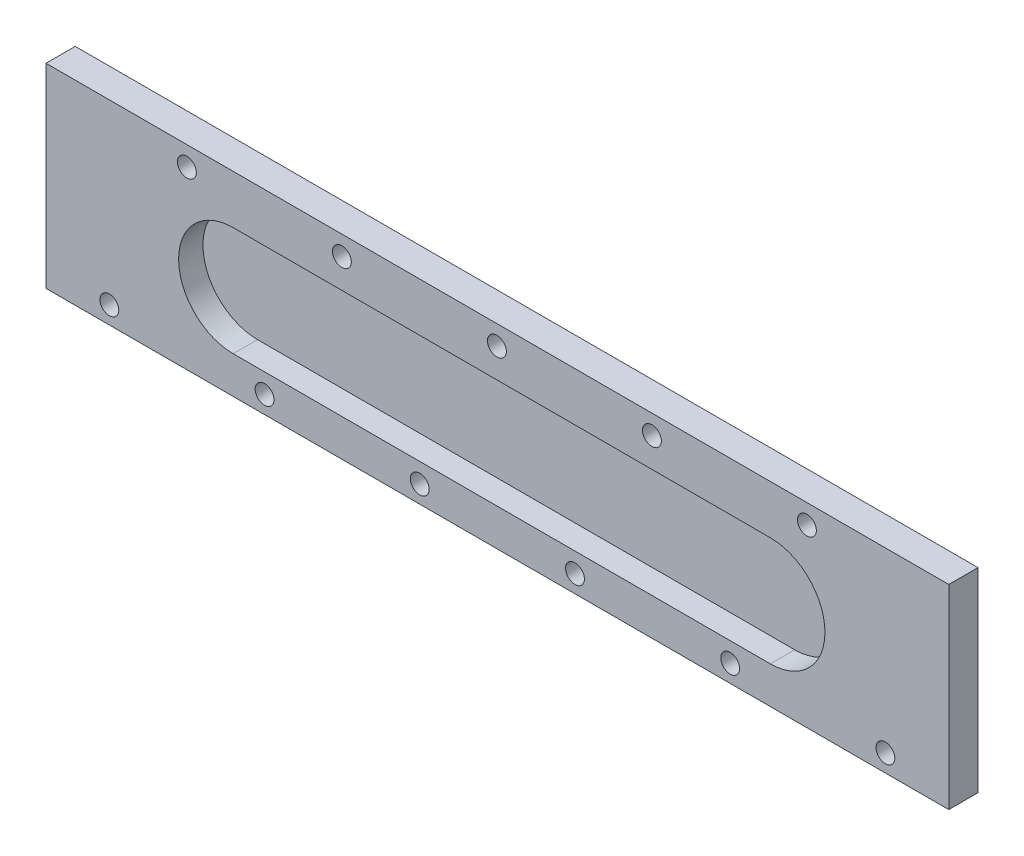
SolidWorks part; units mm, degrees
ref_plane "Front Plane" through (0, 0, 0) normal (0, 0, 1) x (1, 0, 0)
ref_plane "Top Plane" through (0, 0, 0) normal (0, 1, 0) x (1, 0, 0)
ref_plane "Right Plane" through (0, 0, 0) normal (1, 0, 0) x (0, 0, -1)
sketch "Sketch5" plane through (0, 0, 0) normal (0, 0, 1) x (1, 0, 0)
  line L1 (0, 0) -> (-235.204, 0)
  line L2 (0, 0) -> (0, 50.8)
  line L3 (0, 50.8) -> (-235.204, 50.8)
  line L4 (-235.204, 0) -> (-235.204, 50.8)
  dimension "D1" = 235.204
  dimension "D2" = 50.8
extrude "Boss-Extrude3" add sketch "Sketch5" along normal blind 7.62
sketch "Sketch6" plane through (0, 0, 7.62) normal (0, 0, 1) x (1, 0, 0)
  line L0 (-235.204, 50.8) -> (-235.204, 0) construction
  line L2 (0, 0) -> (0, 50.8) construction
  line L3 (-46.482, 23.876) -> (-186.436, 23.876) construction
  line L4 (0, 50.8) -> (-235.204, 50.8) construction
  line L7 (-46.482, 9.652) -> (-186.436, 9.652)
  line L8 (-46.482, 38.1) -> (-186.436, 38.1)
  arc A0 (-46.482, 9.652) -> (-46.482, 38.1) centre (-46.482, 23.876) ccw
  arc A1 (-186.436, 38.1) -> (-186.436, 9.652) centre (-186.436, 23.876) ccw
  point P2 (-32.258, 23.876)
  point P5 (-200.66, 23.876)
  point P9 (-235.204, 25.4)
  point P14 (-116.459, 23.876)
  dimension "D4" = 32.258
  dimension "D1" = 28.448
  dimension "D3" = 12.7
  dimension "D5" = 34.544
extrude "Cut-Extrude3" cut sketch "Sketch6" against normal blind 6.35
sketch "Sketch7" plane through (0, 0, 7.62) normal (0, 0, 1) x (1, 0, 0)
  line L0 (-235.204, 50.8) -> (-235.204, 0) construction
  line L1 (0, 0) -> (0, 50.8) construction
  line L2 (0, 50.8) -> (-235.204, 50.8) construction
  circle A0 centre (-218.694, 4.5485) radius 1.7923
  circle A1 centre (-178.2572, 4.5485) radius 1.7923
  circle A2 centre (-137.8204, 4.5485) radius 1.7923
  circle A3 centre (-97.3836, 4.5485) radius 1.7923
  circle A4 centre (-56.9468, 4.5485) radius 1.7923
  circle A5 centre (-16.51, 4.5485) radius 1.7923
  circle A6 centre (-198.501, 45.72) radius 3.5223
  circle A7 centre (-158.115, 45.72) radius 3.5223
  circle A8 centre (-117.729, 45.72) radius 3.5223
  circle A9 centre (-77.343, 45.72) radius 3.5223
  circle A10 centre (-36.957, 45.72) radius 2.697
  dimension "D2" = 16.51
  dimension "D4" = 40.4368
  dimension "D6" = 20.193
  dimension "D8" = 40.386
  dimension "D3" = 16.51
  dimension "D7" = 40.386
  dimension "D9" = 5.08
  dimension "D10" = 5.08
  dimension "D1" = 6
  dimension "D5" = 4
hole_wizard "#10 (0.1935) Diameter Hole1" positions "3DSketch1" profile "Sketch8" hole size "#10" standard "ANSI Inch" end condition through all
sketch3d "3DSketch1"
  point P0 (-198.501, 45.72, 7.62)
  point P3 (-158.115, 45.72, 7.62)
  point P6 (-117.729, 45.72, 7.62)
  point P9 (-77.343, 45.72, 7.62)
  point P12 (-36.957, 45.72, 7.62)
  point P15 (-218.694, 4.5485, 7.62)
  point P18 (-178.2572, 4.5485, 7.62)
  point P21 (-137.8204, 4.5485, 7.62)
  point P24 (-97.3836, 4.5485, 7.62)
  point P27 (-56.9468, 4.5485, 7.62)
  point P30 (-16.51, 4.5485, 7.62)
sketch "Sketch8" plane through (-198.501, 45.72, 7.62) normal (1, 0, 0) x (0, -1, 0)
  line L0 (0, 0) -> (0, 7.62)
  line L1 (0, 7.62) -> (2.4574, 7.62)
  line L2 (2.4574, 7.62) -> (2.4574, 0)
  line L5 (2.4574, 0) -> (0, 0)
  line L11 (0, -6.35) -> (0, 107.95) construction
  dimension "Thru Hole Dia." = 4.9149
  dimension "Thru Hole Depth" = 7.62
